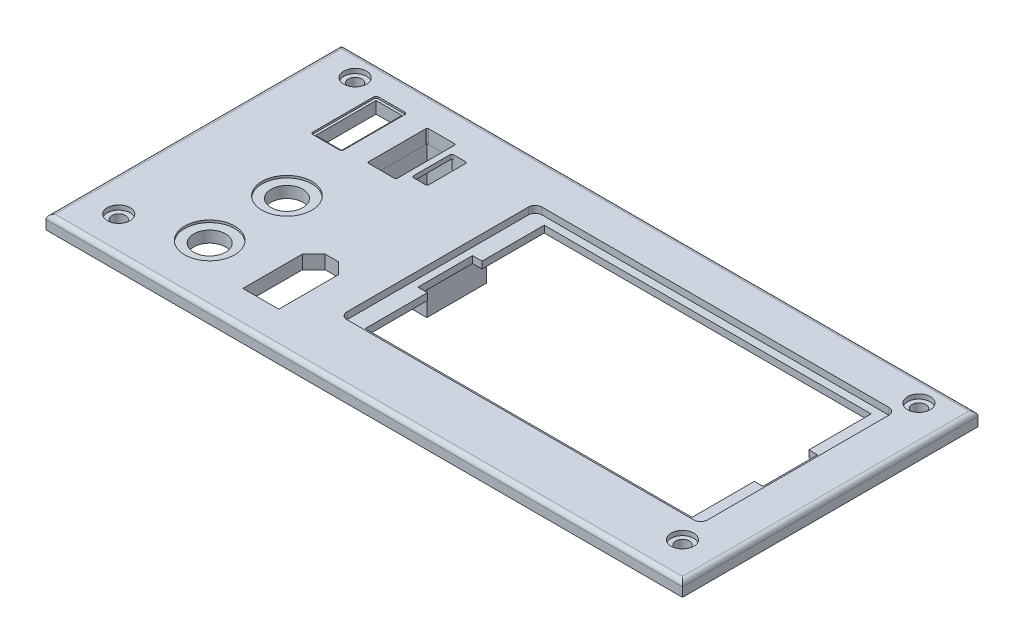
SolidWorks part; units mm, degrees
ref_plane "Спереди" through (0, 0, 0) normal (0, 0, 1) x (1, 0, 0)
ref_plane "Сверху" through (0, 0, 0) normal (0, 1, 0) x (1, 0, 0)
ref_plane "Справа" through (0, 0, 0) normal (1, 0, 0) x (0, 0, -1)
sketch "Эскиз1" plane through (0, 0, 0) normal (0, 1, 0) x (1, 0, 0)
  line L1 (-60, 30) -> (80, 30)
  line L2 (-60, 30) -> (-60, -35)
  line L3 (-60, -35) -> (80, -35)
  line L4 (80, 30) -> (80, -35)
  line L5 (-60, 30) -> (80, -35) construction
  line L6 (-60, -35) -> (80, 30) construction
  point P0 (0, 0)
  dimension "D1" = 65
  dimension "D2" = 140
extrude "Передняя панель основа" add sketch "Эскиз1" along normal blind 3
sketch "Эскиз2" plane through (0, 3, 0) normal (0, 1, 0) x (1, 0, 0)
  line L1 (71, 20.9) -> (-8.3, 20.9)
  line L2 (71, 20.9) -> (71, -22)
  line L3 (71, -22) -> (-8.3, -22)
  line L4 (-8.3, 20.9) -> (-8.3, -22)
  line L5 (71, 20.9) -> (-8.3, -22) construction
  line L6 (71, -22) -> (-8.3, 20.9) construction
  point P0 (31.35, -0.55)
  dimension "D1" = 42.9
  dimension "D2" = 79.3
  dimension "D3" = 13
  dimension "D4" = 9
extrude "Внешняя рамка модуля" cut sketch "Эскиз2" against normal blind 1.5
fillet "Уголки скругления рамки выреза модуля" radius 1.5 4 edges at (71, 2.25, 22) (-8.3, 2.25, 22) (71, 2.25, -20.9) (-8.3, 2.25, -20.9)
sketch "Эскиз3" plane through (0, 1.5, 0) normal (0, 1, 0) x (1, 0, 0)
  line L0 (-60, -35) -> (80, -35) construction
  line L1 (-4.6, 19.2) -> (67.3, 19.2)
  line L2 (-4.6, 19.2) -> (-4.6, -20.2)
  line L3 (-4.6, -20.2) -> (67.3, -20.2)
  line L4 (67.3, 19.2) -> (67.3, -20.2)
  line L5 (-4.6, 19.2) -> (67.3, -20.2) construction
  line L6 (-4.6, -20.2) -> (67.3, 19.2) construction
  line L7 (69.5, 20.9) -> (-6.8, 20.9) construction
  line L8 (-6.8, -22) -> (69.5, -22) construction
  line L9 (71, -20.5) -> (71, 19.4) construction
  line L10 (-8.3, 19.4) -> (-8.3, -20.5) construction
  point P0 (31.35, -0.5)
  dimension "D1" = 39.4
  dimension "D2" = 71.9
  dimension "D3" = 14.8
  dimension "D4" = 12.7
  dimension "D5" = 1.7
  dimension "D6" = 1.8
  dimension "D7" = 3.7
  dimension "D8" = 3.7
extrude "Вырез тела модуля" cut sketch "Эскиз3" against normal blind 3
sketch "Эскиз4" plane through (0, 1.5, 0) normal (0, 1, 0) x (1, 0, 0)
  line L0 (-4.6, 19.2) -> (-4.6, -20.2) construction
  line L1 (-2.5, -6.5) -> (-6.7, -6.5)
  line L2 (-2.5, -6.5) -> (-2.5, 5.5)
  line L3 (-2.5, 5.5) -> (-6.7, 5.5)
  line L4 (-6.7, -6.5) -> (-6.7, 5.5)
  line L5 (-2.5, -6.5) -> (-6.7, 5.5) construction
  line L6 (-2.5, 5.5) -> (-6.7, -6.5) construction
  line L7 (69.2, -6.5) -> (69.2, 5.5)
  line L8 (69.2, -6.5) -> (65, -6.5)
  line L9 (65, -6.5) -> (65, 5.5)
  line L10 (69.2, 5.5) -> (65, 5.5)
  point P0 (-4.6, -0.5)
  dimension "D1" = 12
  dimension "D2" = 4.2
  dimension "D3" = 2
extrude "Ушки модуля" cut sketch "Эскиз4" against normal blind 3
sketch "Эскиз5" plane through (0, 3, 0) normal (0, 1, 0) x (1, 0, 0)
  line L1 (-60, -35) -> (80, -35) construction
  line L2 (-60, 30) -> (-60, -35) construction
  circle A0 centre (-37, -5) radius 5.5
  circle A1 centre (-37, -22) radius 5.5
  dimension "D1" = 11
  dimension "D2" = 11
  dimension "D3" = 13
  dimension "D4" = 23
  dimension "D5" = 17
extrude "Внешние кольца под бананы" cut sketch "Эскиз5" against normal blind 0.5
sketch "Эскиз6" plane through (0, 2.5, 0) normal (0, 1, 0) x (1, 0, 0)
  circle A0 centre (-37, -5) radius 3.5
  circle A1 centre (-37, -22) radius 3.5
  dimension "D1" = 7
  dimension "D2" = 7
extrude "Вырез под бананы" cut sketch "Эскиз6" against normal blind 3
sketch "Эскиз7" plane through (0, 3, 0) normal (0, 1, 0) x (1, 0, 0)
  line L1 (-46.3, 23.9) -> (-39.5, 23.9)
  line L2 (-46.3, 23.9) -> (-46.3, 9.5)
  line L3 (-46.3, 9.5) -> (-39.5, 9.5)
  line L4 (-39.5, 23.9) -> (-39.5, 9.5)
  line L5 (-46.3, 23.9) -> (-39.5, 9.5) construction
  line L6 (-46.3, 9.5) -> (-39.5, 23.9) construction
  line L10 (-8.3, 19.4) -> (-8.3, -20.5) construction
  line L11 (69.5, 20.9) -> (-6.8, 20.9) construction
  circle A0 centre (-37, -5) radius 5.5 construction
  point P0 (-42.9, 16.7)
  dimension "D1" = 14.4
  dimension "D2" = 6.8
  dimension "D4" = 2.5
extrude "Внешняя рамка USB" cut sketch "Эскиз7" against normal blind 0.4
sketch "Эскиз8" plane through (0, 2.6, 0) normal (0, 1, 0) x (1, 0, 0)
  line L0 (-39.5, 23.9) -> (-46.3, 23.9) construction
  line L1 (-45.75, 23.35) -> (-40.05, 23.35)
  line L2 (-45.75, 23.35) -> (-45.75, 10.05)
  line L3 (-45.75, 10.05) -> (-40.05, 10.05)
  line L4 (-40.05, 23.35) -> (-40.05, 10.05)
  line L5 (-45.75, 23.35) -> (-40.05, 10.05) construction
  line L6 (-45.75, 10.05) -> (-40.05, 23.35) construction
  line L7 (-46.3, 9.5) -> (-39.5, 9.5) construction
  line L8 (-46.3, 23.9) -> (-46.3, 9.5) construction
  line L9 (-39.5, 9.5) -> (-39.5, 23.9) construction
  point P0 (-42.9, 16.7)
  dimension "D1" = 13.3
  dimension "D2" = 5.7
  dimension "D3" = 0.55
  dimension "D4" = 0.55
  dimension "D5" = 0.55
  dimension "D6" = 0.55
extrude "USB" cut sketch "Эскиз8" against normal blind 3
fillet "Скругление уголков 1 USB" radius 0.5 4 edges at (-46.3, 2.8, -9.5) (-39.5, 2.8, -9.5) (-39.5, 2.8, -23.9) (-46.3, 2.8, -23.9)
sketch "Эскиз9" plane through (0, 3, 0) normal (0, 1, 0) x (1, 0, 0)
  line L0 (-24.2, -27.5) -> (-16.3, -27.5)
  line L1 (-16.3, -27.5) -> (-16.3, -14.4)
  line L2 (-16.3, -14.4) -> (-18.8, -11.9)
  line L3 (-18.8, -11.9) -> (-21.7, -11.9)
  line L4 (-21.7, -11.9) -> (-24.2, -14.4)
  line L5 (-24.2, -14.4) -> (-24.2, -27.5)
  line L6 (-46.3, 23.4) -> (-46.3, 10) construction
  line L7 (-60, -35) -> (80, -35) construction
  line L8 (-8.3, 19.4) -> (-8.3, -20.5) construction
  line L9 (-60, 30) -> (-60, -35) construction
  circle A3 centre (-37, -22) radius 5.5 construction
  point P8 (-20.25, -27.5)
  point P9 (-20.25, -11.9)
  dimension "D4" = 7.5
  dimension "D1" = 7.9
  dimension "D2" = 15.6
  dimension "D3" = 2.5
  dimension "D5" = 8
  dimension "D6" = 12.8
  dimension "D7" = 35.8
extrude "XT60 на передней панели" cut sketch "Эскиз9" against normal through all
sketch "Эскиз10" plane through (0, 3, 0) normal (0, 1, 0) x (1, 0, 0)
  line L0 (80, 30) -> (-60, 30) construction
  line L1 (-60, 30) -> (-60, -35) construction
  line L2 (80, -35) -> (80, 30) construction
  line L3 (-60, -35) -> (80, -35) construction
  circle A0 centre (-52, 25) radius 1.5
  circle A1 centre (72, 25) radius 1.5
  circle A2 centre (72, -27) radius 1.5
  circle A3 centre (-52, -27) radius 1.5
  dimension "D1" = 3
  dimension "D2" = 5
  dimension "D3" = 8
  dimension "D5" = 8
  dimension "D6" = 5
  dimension "D7" = 8
  dimension "D8" = 8
  dimension "D9" = 8
  dimension "D10" = 8
  dimension "D4" = 2
extrude "Отверстия крепления передней панели к корпусу" cut sketch "Эскиз10" against normal through all
sketch "Эскиз13" plane through (0, 3, 0) normal (0, 1, 0) x (1, 0, 0)
  circle A0 centre (-52, 25) radius 2.5
  circle A1 centre (72, 25) radius 2.5
  circle A2 centre (72, -27) radius 2.5
  circle A3 centre (-52, -27) radius 2.5
  dimension "D1" = 5
  dimension "D2" = 2
extrude "Фаска под головку болта передней панели" cut sketch "Эскиз13" against normal blind 1
fillet "Скругление1" radius 1 4 edges at (10, 3, 35) (80, 3, 2.5) (-60, 3, 2.5) (10, 3, -30)
sketch "Эскиз14" plane through (0, 3, 0) normal (0, 1, 0) x (1, 0, 0)
  line L0 (-28.2, 10.15) -> (-34.5, 10.15)
  line L1 (-34.5, 10.15) -> (-34.5, 23.35)
  line L2 (-34.5, 23.35) -> (-28.2, 23.35)
  line L3 (-28.2, 23.35) -> (-28.2, 25.9)
  line L4 (-28.2, 25.9) -> (-26.9, 25.9)
  line L5 (-26.9, 25.9) -> (-26.9, 21.15)
  line L6 (-26.9, 21.15) -> (-23.5, 21.15)
  line L7 (-23.5, 21.15) -> (-23.5, 12.35)
  line L8 (-23.5, 12.35) -> (-26.9, 12.35)
  line L9 (-26.9, 12.35) -> (-26.9, 7.6)
  line L10 (-26.9, 7.6) -> (-28.2, 7.6)
  line L11 (-28.2, 7.6) -> (-28.2, 10.15)
  line L12 (-40.05, 23.35) -> (-45.75, 23.35) construction
  circle A0 centre (-37, -5) radius 3.5 construction
  dimension "D1" = 13.2
  dimension "D2" = 11
  dimension "D3" = 6.3
  dimension "D4" = 1.3
  dimension "D5" = 3.4
  dimension "D6" = 8.8
  dimension "D7" = 18.3
  dimension "D8" = 2.5
extrude "Вырез-Вытянуть1" cut sketch "Эскиз14" against normal blind 3
fillet "Скругление2" radius 0.4 2 edges at (-23.5, 1.5, -12.35) (-23.5, 1.5, -21.15)
fillet "Скругление3" radius 0.3 2 edges at (-34.5, 1.5, -10.15) (-34.5, 1.5, -23.35)
sketch "Эскиз15" plane through (0, 3, 0) normal (0, 1, 0) x (1, 0, 0)
  line L1 (-28.2, 26) -> (-26.9, 26)
  line L2 (-28.2, 26) -> (-28.2, 7.6)
  line L3 (-28.2, 7.6) -> (-26.9, 7.6)
  line L4 (-26.9, 26) -> (-26.9, 7.6)
  line L5 (-28.2, 26) -> (-26.9, 7.6) construction
  line L6 (-28.2, 7.6) -> (-26.9, 26) construction
  line L11 (-26.9, 25.9) -> (-28.2, 25.9) construction
  line L12 (-28.2, 7.6) -> (-26.9, 7.6) construction
  line L15 (-28.2, 25.9) -> (-28.2, 23.35) construction
  point P0 (-27.55, 16.8)
  point P9 (0, 0)
  point P10 (-27.55, 7.6)
  dimension "D1" = 18.4
extrude "Бобышка-Вытянуть1" add sketch "Эскиз15" against normal blind 1
fillet "Скругление4" radius 0.3 2 edges at (-28.2, 2.5, -10.15) (-28.2, 2.5, -23.35)
fillet "Скругление5" radius 0.4 2 edges at (-26.9, 2.5, -12.35) (-26.9, 2.5, -21.15)
sketch "Эскиз17" plane through (0, 0, 0) normal (0, -1, 0) x (1, 0, 0)
  line L0 (-34.6184, -9.9961) -> (-28.3093, -9.9961)
  line L1 (-28.3093, -9.9961) -> (-28.3093, -7.5533)
  line L2 (-28.3093, -7.5533) -> (-26.7705, -7.5533)
  line L3 (-26.7705, -7.5533) -> (-26.7705, -12.1697)
  line L4 (-26.7705, -12.1697) -> (-23.4044, -12.1697)
  line L5 (-23.4044, -12.1697) -> (-23.4044, -21.2455)
  line L6 (-23.4044, -21.2455) -> (-26.7705, -21.2455)
  line L7 (-26.7705, -21.2455) -> (-26.7705, -25.9546)
  line L8 (-26.7705, -25.9546) -> (-28.3093, -25.9546)
  line L9 (-28.3093, -25.9546) -> (-28.3093, -23.4086)
  line L10 (-28.3093, -23.4086) -> (-34.6184, -23.4086)
  line L11 (-34.6184, -23.4086) -> (-34.6184, -9.9961)
extrude "Вытянуть-Тонкостенный1" add sketch "Эскиз17" along normal blind 20 thin thin type one direction wall 2
